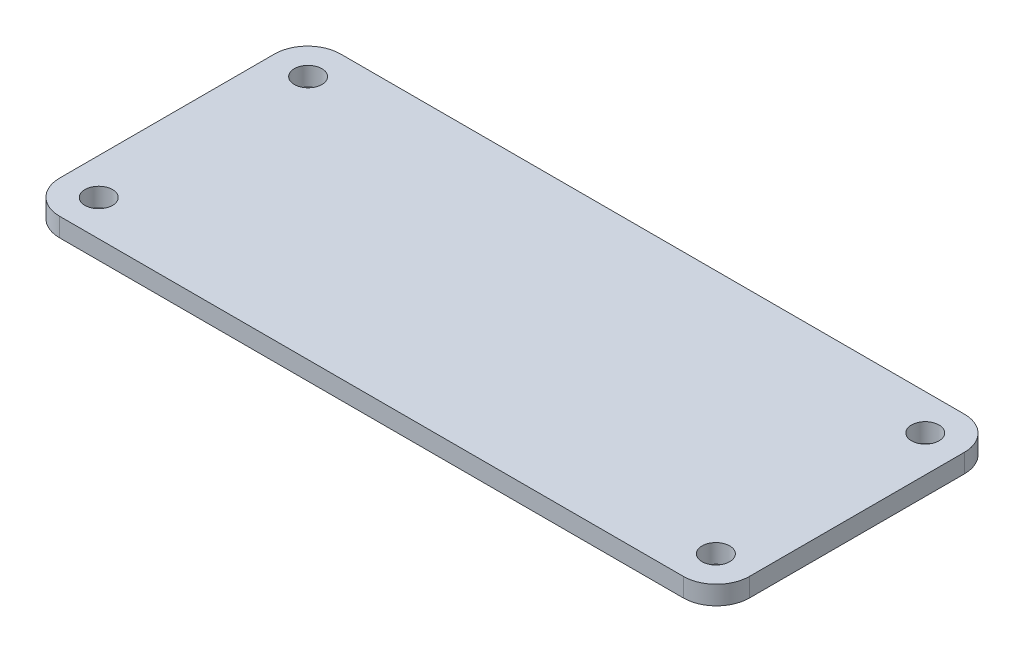
SolidWorks part; units mm, degrees
ref_plane "Front Plane" through (0, 0, 0) normal (0, 0, 1) x (1, 0, 0)
ref_plane "Top Plane" through (0, 0, 0) normal (0, 1, 0) x (1, 0, 0)
ref_plane "Right Plane" through (0, 0, 0) normal (1, 0, 0) x (0, 0, -1)
ref_axis "X" through (-88.99, 0, 0) along (1, 0, 0)
ref_axis "Y" through (0, 55, 0) along (0, -1, 0)
ref_axis "Z" through (0, 0, -88.99) along (0, 0, 1)
sketch "Sketch1" plane through (0, 0, 0) normal (0, 1, 0) x (1, 0, 0)
  line L1 (-31.3, 12.75) -> (31.3, 12.75)
  line L2 (-31.3, 12.75) -> (-31.3, -12.75)
  line L3 (-31.3, -12.75) -> (31.3, -12.75)
  line L4 (31.3, 12.75) -> (31.3, -12.75)
  line L5 (-31.3, 12.75) -> (31.3, -12.75) construction
  line L6 (-31.3, -12.75) -> (31.3, 12.75) construction
  line L7 (-28, 9.5) -> (28, 9.5) construction
  line L8 (-28, 9.5) -> (-28, -9.5) construction
  line L9 (-28, -9.5) -> (28, -9.5) construction
  line L10 (28, 9.5) -> (28, -9.5) construction
  line L11 (-28, 9.5) -> (28, -9.5) construction
  line L12 (-28, -9.5) -> (28, 9.5) construction
  circle A0 centre (-28, 9.5) radius 1.25
  circle A1 centre (28, 9.5) radius 1.25
  circle A2 centre (28, -9.5) radius 1.25
  circle A3 centre (-28, -9.5) radius 1.25
  point P0 (0, 0)
  point P5 (0, 0)
  dimension "D5" = 2.5
  dimension "D1" = 25.5
  dimension "D2" = 62.6
  dimension "D3" = 19
  dimension "D4" = 56
extrude "Boss-Extrude1" add sketch "Sketch1" along normal blind 1.7
fillet "Fillet1" radius 3 4 edges at (31.3, 0.85, -12.75) (31.3, 0.85, 12.75) (-31.3, 0.85, -12.75) (-31.3, 0.85, 12.75)
